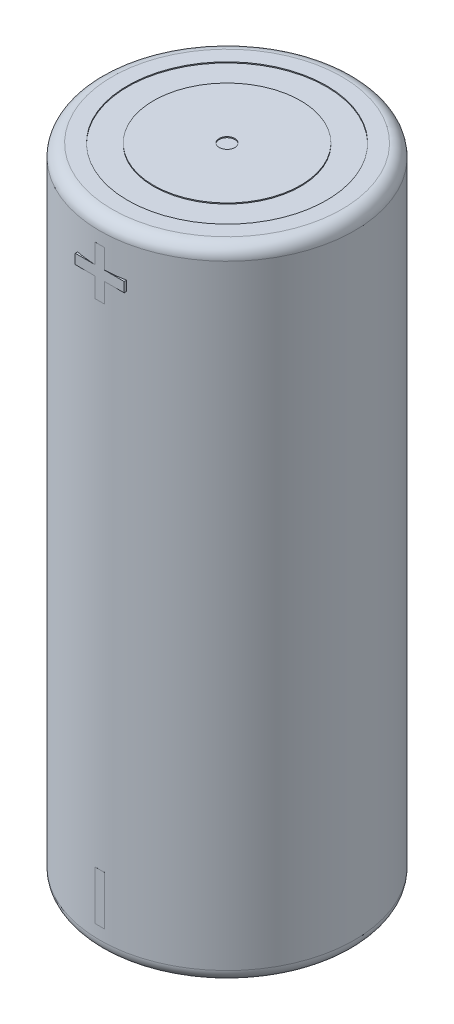
SolidWorks part; units mm, degrees
ref_plane "Front Plane" through (0, 0, 0) normal (0, 0, 1) x (1, 0, 0)
ref_plane "Top Plane" through (0, 0, 0) normal (0, 1, 0) x (1, 0, 0)
ref_plane "Right Plane" through (0, 0, 0) normal (1, 0, 0) x (0, 0, -1)
sketch "Sketch1" plane through (0, 0, 0) normal (0, 1, 0) x (1, 0, 0)
  circle A0 centre (0, 0) radius 13
  dimension "D1" = 26
extrude "Boss-Extrude1" add sketch "Sketch1" along normal blind 65.25
fillet "Fillet1" radius 1.27 1 edges at (0, 65.25, 13)
fillet "Fillet2" radius 1.27 1 edges at (0, 0, 13)
ref_plane "Plane1" through (0, 0, 13) normal (0, 0, 1) x (1, 0, 0)
sketch "Sketch2" plane through (0, 0, 13) normal (0, 0, 1) x (1, 0, 0)
  line L0 (11.73, 65.25) -> (-11.73, 65.25) construction
  line L1 (11.73, 65.25) -> (-11.73, 65.25)
  line L2 (0, 65.25) -> (0, 0) construction
  line L4 (-0.5, 62.75) -> (0.5, 62.75)
  line L5 (-0.5, 62.75) -> (-0.5, 57.75)
  line L6 (-0.5, 57.75) -> (0.5, 57.75)
  line L7 (0.5, 62.75) -> (0.5, 57.75)
  line L8 (-2.5, 60.75) -> (2.5, 60.75)
  line L9 (-2.5, 60.75) -> (-2.5, 59.75)
  line L10 (-2.5, 59.75) -> (2.5, 59.75)
  line L11 (2.5, 60.75) -> (2.5, 59.75)
  line L12 (-0.5, 7.5) -> (0.5, 7.5)
  line L13 (-0.5, 7.5) -> (-0.5, 2.5)
  line L14 (-0.5, 2.5) -> (0.5, 2.5)
  line L15 (0.5, 7.5) -> (0.5, 2.5)
  point P13 (0, 60.25)
  point P18 (0, 5)
  dimension "D1" = 5
  dimension "D2" = 5
  dimension "D3" = 1
  dimension "D4" = 1
  dimension "D5" = 0.5
  dimension "D6" = 2.5
  dimension "D7" = 5
  dimension "D8" = 0.5
  dimension "D9" = 2.5
  dimension "D10" = 1
  dimension "D11" = 5
  dimension "D12" = 5
  dimension "D13" = 2.5
  dimension "D14" = 0.5
extrude "Boss-Extrude2" add sketch "Sketch2" against normal blind 10 contours L2 L12 L13 L14 | L12 L2 L14 L15 | L5 L6 L7 L4 | L8 L11 L10 L9 region at (0.25, 5, 13) region at (-0.25, 5, 13)
sketch "Sketch3" plane through (0, 65.25, 0) normal (0, 1, 0) x (1, 0, 0)
  point P0 (0, 0)
sketch "Sketch4" plane through (0, 0, 0) normal (0, -1, 0) x (-1, 0, 0)
  point P0 (0, 0)
sketch "Sketch5" plane through (0, 65.25, 0) normal (0, 1, 0) x (1, 0, 0)
  circle A0 centre (0, 0) radius 10.15
  circle A1 centre (0, 0) radius 7.5
  circle A2 centre (0, 0) radius 0.8
  dimension "D1" = 20.3
  dimension "D2" = 15
extrude "Cut-Extrude1" cut sketch "Sketch5" against normal blind 0.1 contours A0 A1 | A2 region at (-9.8629, 65.25, 0) region at (0, 65.25, 0)
sketch "Sketch6" plane through (0, 0, 0) normal (0, -1, 0) x (1, 0, 0)
  circle A0 centre (0, 0) radius 9.2
  circle A1 centre (0, 0) radius 7.15
  dimension "D1" = 18.4
  dimension "D2" = 14.3
extrude "Cut-Extrude2" cut sketch "Sketch6" against normal blind 0.1 contours A0 A1 region at (-8.9398, 0, 0)
sketch "Sketch7" plane through (0, 0, 0) normal (0, -1, 0) x (1, 0, 0)
  circle A0 centre (0, 0) radius 6.35
  circle A1 centre (0, 0) radius 1.625
  circle A2 centre (0, 0) radius 7.15
  circle A3 centre (0, 0) radius 7.15
  circle M3 centre (0, 0) radius 7.15
  dimension "D2" = 12.7
  dimension "D3" = 3.25
  dimension "D1" = 0
extrude "Cut-Extrude3" cut sketch "Sketch7" against normal blind 0.25 contours A0 M3 | A1 region at (0, 0, 0) region at (-6.9478, 0, 0)
chamfer "Chamfer1" distance 0.1 angle 45 1 edges at (0, 0, -6.35)
